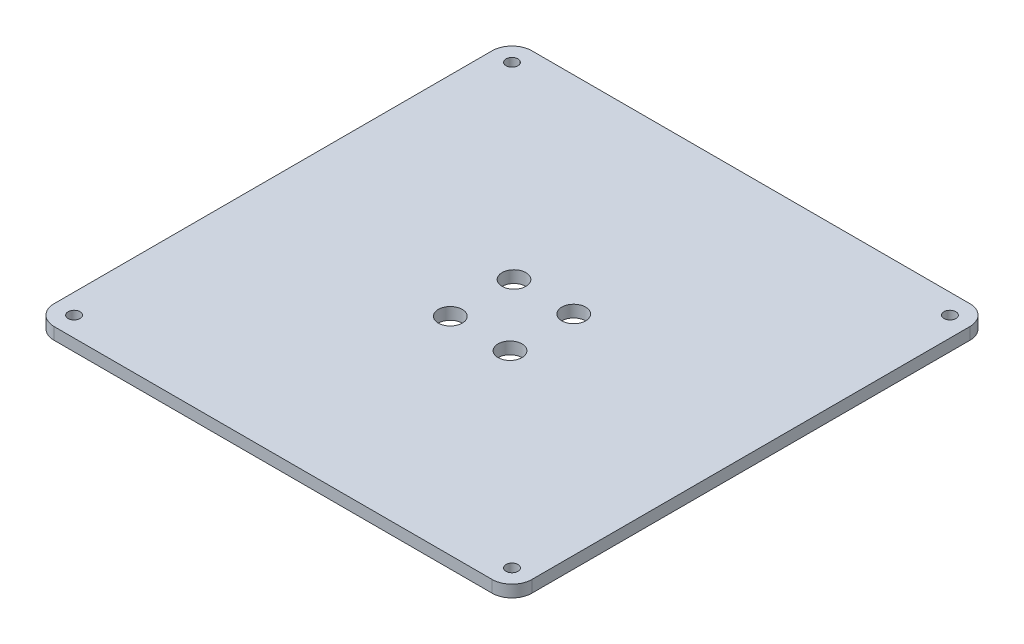
SolidWorks part; units mm, degrees
material "ABS"
ref_plane "Alzado" through (0, 0, 0) normal (0, 0, 1) x (1, 0, 0)
ref_plane "Planta" through (0, 0, 0) normal (0, 1, 0) x (1, 0, 0)
ref_plane "Vista lateral" through (0, 0, 0) normal (1, 0, 0) x (0, 0, -1)
sketch "Sketch1" plane through (0, 0, 0) normal (0, 1, 0) x (1, 0, 0)
  line L1 (-7.5, -8) -> (7.5, -8) construction
  line L2 (-7.5, -8) -> (-7.5, 8) construction
  line L3 (-7.5, 8) -> (7.5, 8) construction
  line L4 (7.5, -8) -> (7.5, 8) construction
  line L5 (-7.5, -8) -> (7.5, 8) construction
  line L6 (-7.5, 8) -> (7.5, -8) construction
  line L7 (-60, -60) -> (60, -60)
  line L8 (-60, -60) -> (-60, 60)
  line L9 (-60, 60) -> (60, 60)
  line L10 (60, -60) -> (60, 60)
  line L11 (-60, -60) -> (60, 60) construction
  line L12 (-60, 60) -> (60, -60) construction
  circle A0 centre (-7.5, -8) radius 3
  circle A1 centre (7.5, 8) radius 3
  circle A2 centre (7.5, -8) radius 3
  circle A3 centre (-7.5, 8) radius 3
  point P0 (0, 0)
  point P10 (0, 0)
  point P17 (-48.6739, 48.6739)
  dimension "D3" = 6
  dimension "D1" = 16
  dimension "D2" = 15
  dimension "D4" = 120
  dimension "D5" = 120
extrude "Boss-Extrude1" add sketch "Sketch1" along normal blind 3
fillet "Fillet1" radius 5 4 edges at (-60, 1.5, -60) (60, 1.5, -60) (60, 1.5, 60) (-60, 1.5, 60)
sketch "Sketch2" plane through (0, 3, 0) normal (0, 1, 0) x (1, 0, 0)
  line L0 (-55, 55) -> (-55, 60) construction
  line L1 (-55, 55) -> (-60, 55) construction
  circle A0 centre (-55, 55) radius 1.5
  dimension "D1" = 3
extrude "Cut-Extrude1" cut sketch "Sketch2" against normal through all
mirror "Mirror3" about plane through (0, 0, 0) normal (0, 0, 1) of "Cut-Extrude1" second plane through (0, 0, 0) second plane normal (1, 0, 0)
